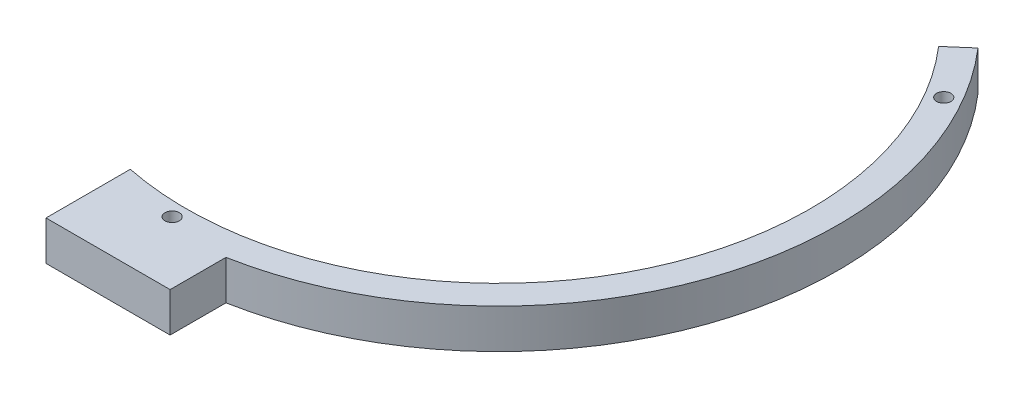
SolidWorks part; units mm, degrees
ref_plane "Front Plane" through (0, 0, 0) normal (0, 0, 1) x (1, 0, 0)
ref_plane "Top Plane" through (0, 0, 0) normal (0, 1, 0) x (1, 0, 0)
ref_plane "Right Plane" through (0, 0, 0) normal (1, 0, 0) x (0, 0, -1)
sketch "Sketch1" plane through (0, 0, 0) normal (0, 1, 0) x (1, 0, 0)
  line L0 (-10, -53.8799) -> (-10, -62.8799)
  line L1 (-10, -62.8799) -> (10, -62.8799)
  line L2 (10, -62.8799) -> (10, -53.8799)
  arc A0 (10, -53.8799) -> (-10, -53.8799) centre (0, 0) ccw
  circle A1 centre (0, 0) radius 50.3
  point P9 (0, -62.8799)
  dimension "D1" = 4.5
  dimension "D2" = 109.6
  dimension "D3" = 20
  dimension "D4" = 9
extrude "Boss-Extrude1" add sketch "Sketch1" along normal blind 6.35
sketch "Sketch2" plane through (0, 6.35, 0) normal (0, 1, 0) x (1, 0, 0)
  line L0 (0, -50.3) -> (0, -54.8) construction
  circle A0 centre (0, 0) radius 50.3 construction
  circle A1 centre (0, 0) radius 54.8 construction
  circle A2 centre (0, -52.55) radius 1.15
  dimension "D1" = 2.3
extrude "Cut-Extrude1" cut sketch "Sketch2" against normal up to next
pattern_circular "CirPattern1" count 3 over 360 about axis through (0, 6.35, 0) along (0, 1, 0) of "Cut-Extrude1"
sketch "Sketch3" plane through (0, 6.35, 0) normal (0, 1, 0) x (1, 0, 0)
  line L0 (-10, -53.8799) -> (-10, -49.2959)
  line L1 (41.3769, 35.9304) -> (37.9792, 32.9799)
  line L2 (0, 0) -> (41.3769, 35.9304) construction
  circle A0 centre (0, 0) radius 50.3 construction
  arc A1 (10, -53.8799) -> (-10, -53.8799) centre (0, 0) ccw construction
  circle A2 centre (0, 0) radius 54.8
  circle A3 centre (45.5096, 26.275) radius 1.15 construction
  circle A4 centre (0, 0) radius 50.3
  circle M5 centre (-45.5096, 26.275) radius 1.15
  arc M7 (10, -53.8799) -> (-10, -53.8799) centre (0, 0) ccw
  circle M11 centre (0, 0) radius 50.3
  dimension "D1" = 10
extrude "Cut-Extrude2" cut sketch "Sketch3" against normal up to next contours L1 L0 M7 M11 M5 region at (-47.4408, 6.35, -27.139)
